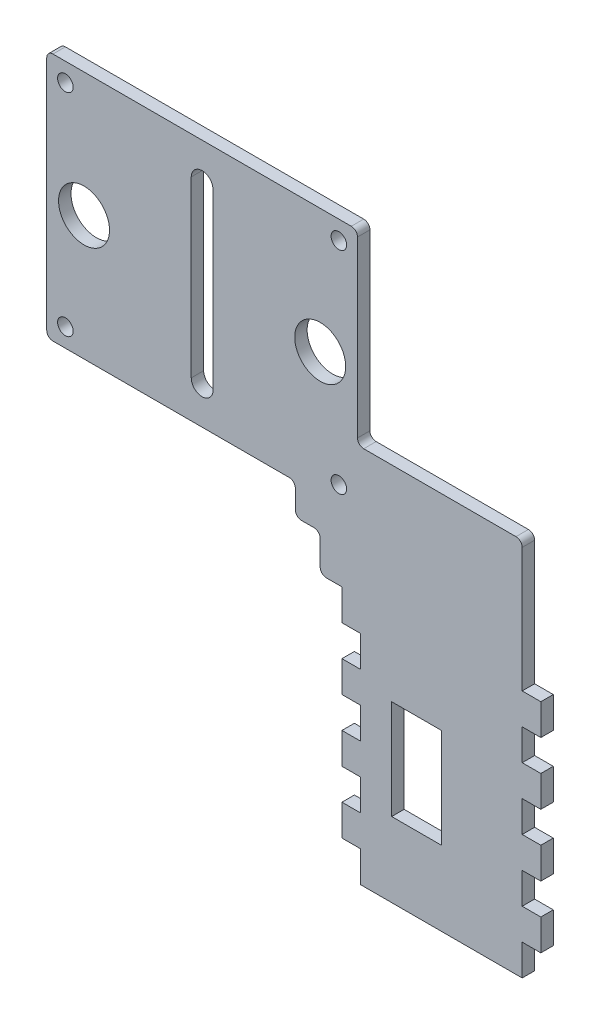
SolidWorks part; units mm, degrees
ref_plane "Front Plane" through (0, 0, 0) normal (0, 0, 1) x (1, 0, 0)
ref_plane "Top Plane" through (0, 0, 0) normal (0, 1, 0) x (1, 0, 0)
ref_plane "Right Plane" through (0, 0, 0) normal (1, 0, 0) x (0, 0, -1)
sketch "Sketch1" plane through (0, 0, 0) normal (0, 0, 1) x (1, 0, 0)
  line L1 (0, 0) -> (50, 0)
  line L2 (0, 0) -> (0, 40)
  line L3 (0, 40) -> (50, 40)
  line L4 (50, 0) -> (50, 40)
  line L5 (50, 0) -> (76.5, 0)
  line L6 (50, 0) -> (50, -51)
  line L7 (50, -51) -> (76.5, -51)
  line L8 (76.5, 0) -> (76.5, -51)
  line L9 (50, 0) -> (76.5, 0)
  line L12 (76.5, 0) -> (76.5, -21)
  line L13 (76.5, 0) -> (50, 0)
  line L14 (76.5, 0) -> (76.5, 10)
  line L15 (76.5, 10) -> (50, 10)
  line L16 (50, 0) -> (50, 10)
  line L17 (40, 0) -> (50, 0)
  line L18 (40, 0) -> (40, -5)
  line L19 (40, -5) -> (50, -5)
  line L20 (50, 0) -> (50, -5)
  line L21 (50, -5) -> (44, -5)
  line L22 (50, -5) -> (50, -11)
  line L23 (50, -11) -> (44, -11)
  line L24 (44, -5) -> (44, -11)
  dimension "D1" = 50
  dimension "D2" = 40
  dimension "D3" = 26.5
  dimension "D4" = 51
  dimension "D5" = 0
  dimension "D6" = 10
  dimension "D7" = 0
  dimension "D8" = 0
  dimension "D9" = 0
  dimension "D10" = 10
  dimension "D11" = 5
  dimension "D12" = 0
  dimension "D13" = 0
  dimension "D14" = 6
  dimension "D15" = 6
extrude "plate_body" add sketch "Sketch1" along normal blind 2 contours L1 L4 L3 L2 | L8 L5 L1 L6 L7 | L14 L15 L4 L5 | L18 L19 L6 L1 | L19 L24 L23 L6 region at (25, 20, 0) region at (45, -2.5, 0) region at (63.25, 5, 0) region at (63.25, -25.5, 0) region at (47, -8, 0)
sketch "Sketch2" plane through (0, 0, 2) normal (0, 0, 1) x (1, 0, 0)
  line L2 (0, 0) -> (0, 40) construction
  line L3 (0, 40) -> (50, 40) construction
  circle A0 centre (6, 20) radius 4.1
  circle A1 centre (44, 20) radius 4.1
  dimension "D1" = 38
  dimension "D2" = 8.2
  dimension "D3" = 8.2
  dimension "D4" = 6
  dimension "D5" = 20
  dimension "D6" = 20
extrude "shaft_bearings" cut sketch "Sketch2" against normal through all
sketch "Sketch4" plane through (0, 0, 2) normal (0, 0, 1) x (1, 0, 0)
  line L0 (25, 34) -> (25, 6) construction
  line L1 (26.75, 34) -> (26.75, 6)
  line L2 (23.25, 34) -> (23.25, 6)
  line L3 (0, 0) -> (40, 0) construction
  line L5 (0, 0) -> (0, 40) construction
  arc A0 (26.75, 34) -> (23.25, 34) centre (25, 34) ccw
  arc A1 (23.25, 6) -> (26.75, 6) centre (25, 6) ccw
  point P2 (25, 20)
  dimension "D4" = 6
  dimension "D1" = 3.5
  dimension "D2" = 28
  dimension "D3" = 25
extrude "slot" cut sketch "Sketch4" against normal through all
sketch "Sketch5" plane through (0, 0, 2) normal (0, 0, 1) x (1, 0, 0)
  line L0 (0, 40) -> (50, 40) construction
  line L1 (0, 0) -> (0, 40) construction
  line L3 (50, 10) -> (50, 40) construction
  line L4 (0, 0) -> (40, 0) construction
  circle A0 centre (3, 37) radius 1.25
  circle A1 centre (47, 37) radius 1.25
  circle A2 centre (3, 3) radius 1.25
  circle A3 centre (47, 3) radius 1.25
  dimension "D1" = 2.5
  dimension "D2" = 2.5
  dimension "D3" = 2.5
  dimension "D4" = 2.5
  dimension "D5" = 3
  dimension "D6" = 3
  dimension "D7" = 3
  dimension "D8" = 3
  dimension "D9" = 3
  dimension "D10" = 3
  dimension "D11" = 3
  dimension "D12" = 3
extrude "bolt_holes" cut sketch "Sketch5" against normal through all
sketch "Sketch6" plane through (0, 0, 2) normal (0, 0, 1) x (1, 0, 0)
  line L0 (50, -51) -> (76.5, -51) construction
  line L1 (50, -11) -> (50.5, -11)
  line L2 (50, -11) -> (50, -51)
  line L3 (50, -51) -> (50.5, -51)
  line L4 (50.5, -11) -> (50.5, -51)
  line L5 (50, -11) -> (44, -11) construction
  dimension "D1" = 0.5
  dimension "D2" = 0
extrude "Cut-Extrude1" cut sketch "Sketch6" against normal through all
sketch "Sketch8" plane through (0, 0, 2) normal (0, 0, 1) x (1, 0, 0)
  line L0 (50.5, -36) -> (47.5, -36)
  line L1 (50.5, -46) -> (47.5, -46)
  line L2 (50.5, -46) -> (50.5, -41)
  line L3 (50.5, -41) -> (47.5, -41)
  line L4 (47.5, -46) -> (47.5, -41)
  line L5 (76.5, -46) -> (79.5, -46)
  line L6 (76.5, -46) -> (76.5, -41)
  line L7 (76.5, -41) -> (79.5, -41)
  line L8 (79.5, -46) -> (79.5, -41)
  line L9 (50.5, -36) -> (50.5, -31)
  line L10 (50.5, -31) -> (47.5, -31)
  line L11 (47.5, -36) -> (47.5, -31)
  line L12 (76.5, -36) -> (79.5, -36)
  line L13 (76.5, -36) -> (76.5, -31)
  line L14 (76.5, -31) -> (79.5, -31)
  line L15 (79.5, -36) -> (79.5, -31)
  line L16 (50.5, -51) -> (50.5, -11) construction
  line L17 (76.5, -51) -> (76.5, 10) construction
  line L18 (50.5, -16) -> (47.5, -16)
  line L19 (50.5, -26) -> (47.5, -26)
  line L20 (50.5, -26) -> (50.5, -21)
  line L21 (50.5, -21) -> (47.5, -21)
  line L22 (47.5, -26) -> (47.5, -21)
  line L23 (76.5, -26) -> (79.5, -26)
  line L24 (76.5, -26) -> (76.5, -21)
  line L25 (76.5, -21) -> (79.5, -21)
  line L26 (79.5, -26) -> (79.5, -21)
  line L27 (50.5, -16) -> (50.5, -11)
  line L28 (50.5, -11) -> (47.5, -11)
  line L29 (47.5, -16) -> (47.5, -11)
  line L30 (76.5, -16) -> (79.5, -16)
  line L31 (76.5, -16) -> (76.5, -11)
  line L32 (76.5, -11) -> (79.5, -11)
  line L33 (79.5, -16) -> (79.5, -11)
  line L34 (50.5, -51) -> (76.5, -51) construction
  point P38 (78, -31)
  point P41 (78, -41)
  dimension "D1" = 5
  dimension "D2" = 5
  dimension "D3" = 3
  dimension "D4" = 3
  dimension "D5" = 5
  dimension "D6" = 5
  dimension "D7" = 3
  dimension "D8" = 3
  dimension "D9" = 0
  dimension "D10" = 0
  dimension "D11" = 5
  dimension "D12" = 5
  dimension "D13" = 5
  dimension "D14" = 5
  dimension "D15" = 3
  dimension "D16" = 3
  dimension "D17" = 5
  dimension "D18" = 5
  dimension "D19" = 3
  dimension "D20" = 3
  dimension "D21" = 5
  dimension "D22" = 5
  dimension "D25" = 0
  dimension "D26" = 0
  dimension "D27" = 5
  dimension "D28" = 5
  dimension "D29" = 10
  dimension "D30" = 10
extrude "finger_joints" add sketch "Sketch8" along direction (0, 0, 1) on the side against the normal up to surface (2 mm away) up to face at (48.25, 37, 0)
sketch "Sketch9" plane through (0, 0, 2) normal (0, 0, 1) x (1, 0, 0)
  line L0 (50.5, -51) -> (76.5, -51) construction
  line L1 (55.5, -23) -> (63.5, -23)
  line L2 (55.5, -23) -> (55.5, -39)
  line L3 (55.5, -39) -> (63.5, -39)
  line L4 (63.5, -23) -> (63.5, -39)
  line L5 (50.5, -51) -> (50.5, -46) construction
  dimension "D1" = 8
  dimension "D2" = 16
  dimension "D3" = 12
  dimension "D4" = 5
extrude "Cut-Extrude2" cut sketch "Sketch9" against normal through all
fillet "1mm_fillets" radius 1 9 edges at (44, -11, 1) (44, -5, 1) (40, -5, 1) (40, 0, 1) (76.5, 10, 1) (50, 10, 1) (50, 40, 1) (0, 0, 1) (0, 40, 1)
